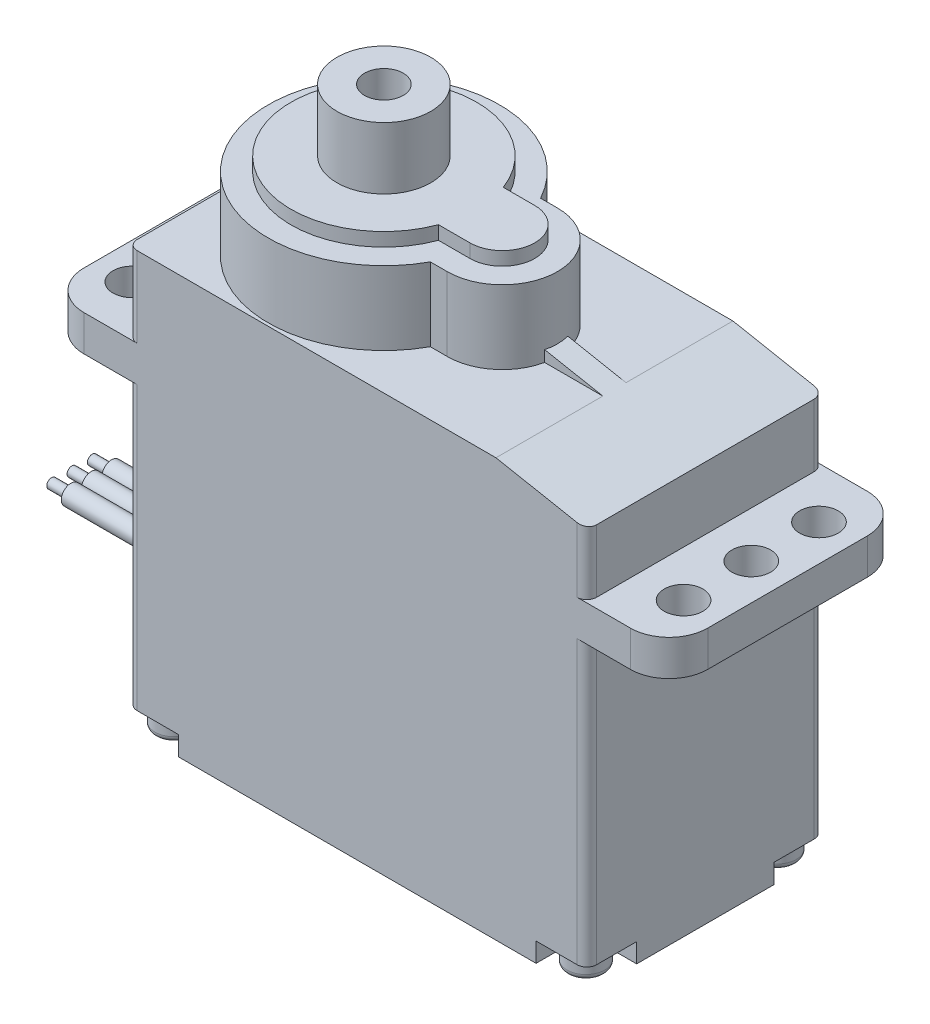
SolidWorks part; units mm, degrees
ref_plane "Front Plane" through (0, 0, 0) normal (0, 0, 1) x (1, 0, 0)
ref_plane "Top Plane" through (0, 0, 0) normal (0, 1, 0) x (1, 0, 0)
ref_plane "Right Plane" through (0, 0, 0) normal (1, 0, 0) x (0, 0, -1)
ref_axis "X-Axis" through (-88.99, 0, 0) along (1, 0, 0)
ref_axis "Y-Axis" through (0, 0, -88.99) along (0, 0, 1)
ref_axis "Z-Axis" through (0, 55, 0) along (0, -1, 0)
sketch "Sketch1" plane through (0, 0, 0) normal (0, 0, 1) x (1, 0, 0)
  line L0 (0, 0) -> (0, 13.7) construction
  line L1 (-7.13, 6) -> (11.92, 6)
  line L2 (-7.13, 6) -> (-7.13, 1.85)
  line L3 (-7.13, -15.6) -> (16.62, -15.6)
  line L4 (16.62, 5.1) -> (16.62, 1.85)
  line L5 (16.62, 1.85) -> (20.87, 1.85)
  line L6 (-11.38, 1.85) -> (-7.13, 1.85)
  line L7 (-11.38, 1.85) -> (-11.38, 0)
  line L8 (-11.38, 0) -> (-7.13, 0)
  line L9 (20.87, 1.85) -> (20.87, 0)
  line L10 (16.62, 0) -> (20.87, 0)
  line L11 (-7.13, 0) -> (-7.13, -15.6)
  line L12 (16.62, 0) -> (16.62, -15.6)
  line L13 (16.62, 5.1) -> (11.92, 6)
  line L14 (16.62, 0) -> (-7.13, 0) construction
  point P3 (4.745, 0)
  dimension "D1" = 1.85
  dimension "D2" = 32.25
  dimension "D3" = 23.75
  dimension "D4" = 15.6
  dimension "D5" = 21.6
  dimension "D6" = 7.13
  dimension "D7" = 16.62
  dimension "D8" = 0.9
  dimension "D9" = 4.7
  dimension "D10" = 29.3
  dimension "D11" = 4.745
extrude "Boss-Extrude1" add sketch "Sketch1" along normal mid plane 12.25
sketch "Sketch2" plane through (0, 6, 0) normal (0, 1, 0) x (1, 0, 0)
  line L0 (0, 0) -> (6.125, 0) construction
  line L1 (5.2515, -2.85) -> (6.125, -2.85)
  line L2 (6.125, 2.85) -> (5.2515, 2.85)
  line L3 (0, 0) -> (-5.975, 0) construction
  line L4 (6.125, 0) -> (8.975, 0) construction
  arc A0 (5.2515, 2.85) -> (5.2515, -2.85) centre (0, 0) ccw
  arc A1 (6.125, -2.85) -> (6.125, 2.85) centre (6.125, 0) ccw
  dimension "D1" = 11.95
  dimension "D2" = 5.7
  dimension "D3" = 14.95
extrude "Boss-Extrude2" add sketch "Sketch2" along normal blind 3.8
sketch "Sketch3" plane through (0, 9.8, 0) normal (0, 1, 0) x (1, 0, 0)
  line L0 (4.4983, -1.675) -> (6.125, -1.675)
  line L1 (6.125, 1.675) -> (4.4983, 1.675)
  line L2 (7.8, 0) -> (8.975, 0) construction
  line L3 (-4.8, 0) -> (-5.975, 0) construction
  arc A0 (4.4983, 1.675) -> (4.4983, -1.675) centre (0, 0) ccw
  arc A1 (6.125, -1.675) -> (6.125, 1.675) centre (6.125, 0) ccw
  arc A2 (6.125, -2.85) -> (6.125, 2.85) centre (6.125, 0) ccw construction
  arc A3 (5.2515, 2.85) -> (5.2515, -2.85) centre (0, 0) ccw construction
  dimension "D1" = 9.6
extrude "Boss-Extrude3" add sketch "Sketch3" along normal blind 0.7
sketch "Sketch4" plane through (0, 0, 0) normal (0, 1, 0) x (1, 0, 0)
  line L0 (-9.505, 0) -> (-7.13, 0) construction
  line L1 (-9.505, 3.5) -> (18.995, 3.5) construction
  line L2 (-9.505, 3.5) -> (-9.505, -3.5) construction
  line L3 (-9.505, -3.5) -> (18.995, -3.5) construction
  line L4 (18.995, 3.5) -> (18.995, -3.5) construction
  line L5 (18.995, 0) -> (16.62, 0) construction
  line L6 (-7.13, -6.125) -> (-7.13, 6.125) construction
  line L7 (16.62, -6.125) -> (16.62, 6.125) construction
  circle A0 centre (-9.505, 3.5) radius 1
  circle A1 centre (-9.505, -3.5) radius 1
  circle A2 centre (18.995, 3.5) radius 1
  circle A3 centre (18.995, -3.5) radius 1
  circle A4 centre (18.995, 0) radius 1
  circle A5 centre (-9.505, 0) radius 1
  dimension "D1" = 2
  dimension "D2" = 28.5
  dimension "D3" = 7
extrude "Cut-Extrude1" cut sketch "Sketch4" along normal through all
sketch "Sketch5" plane through (0, -15.6, 0) normal (0, -1, 0) x (1, 0, 0)
  line L0 (16.62, 6.125) -> (-7.13, -6.125) construction
  line L1 (16.62, 6.125) -> (13.995, 6.125)
  line L2 (16.62, 6.125) -> (16.62, 3.55)
  line L3 (16.62, 3.55) -> (15.295, 3.55)
  line L4 (13.995, 6.125) -> (13.995, 4.85)
  line L5 (16.62, -6.125) -> (13.995, -6.125)
  line L6 (16.62, -6.125) -> (16.62, -3.55)
  line L7 (16.62, -3.55) -> (15.295, -3.55)
  line L8 (13.995, -6.125) -> (13.995, -4.85)
  line L9 (-7.13, 6.125) -> (-4.505, 6.125)
  line L10 (-7.13, 6.125) -> (-7.13, 3.55)
  line L11 (-7.13, 3.55) -> (-5.805, 3.55)
  line L12 (-4.505, 6.125) -> (-4.505, 4.85)
  line L13 (-7.13, -6.125) -> (-4.505, -6.125)
  line L14 (-7.13, -6.125) -> (-7.13, -3.55)
  line L15 (-7.13, -3.55) -> (-5.805, -3.55)
  line L16 (-4.505, -6.125) -> (-4.505, -4.85)
  line L17 (-5.905, 4.95) -> (15.395, 4.95) construction
  line L18 (-5.905, 4.95) -> (-5.905, -4.95) construction
  line L19 (-5.905, -4.95) -> (15.395, -4.95) construction
  line L20 (15.395, 4.95) -> (15.395, -4.95) construction
  line L21 (-5.905, 4.95) -> (15.395, -4.95) construction
  arc A0 (13.995, -4.85) -> (15.295, -3.55) centre (15.295, -4.85) cw
  arc A1 (15.295, 3.55) -> (13.995, 4.85) centre (15.295, 4.85) cw
  arc A2 (-4.505, 4.85) -> (-5.805, 3.55) centre (-5.805, 4.85) cw
  arc A3 (-5.805, -3.55) -> (-4.505, -4.85) centre (-5.805, -4.85) cw
  circle A4 centre (-5.905, 4.95) radius 0.975
  circle A5 centre (-5.905, -4.95) radius 0.975
  circle A6 centre (15.395, -4.95) radius 0.975
  circle A7 centre (15.395, 4.95) radius 0.975
  point P36 (4.745, 0)
  dimension "D1" = 1.3
  dimension "D4" = 1.95
  dimension "D2" = 7.1
  dimension "D3" = 18.5
  dimension "D5" = 21.3
  dimension "D6" = 9.9
extrude "Cut-Extrude2" cut sketch "Sketch5" against normal blind 1
sketch "Sketch6" plane through (-7.13, 0, 0) normal (-1, 0, 0) x (0, 0, 1)
  line L0 (-1.05, -11.7) -> (1.05, -11.7) construction
  line L2 (6.125, 0) -> (-6.125, 0) construction
  circle A0 centre (0, -11.7) radius 0.5
  circle A1 centre (1.05, -11.7) radius 0.5
  circle A2 centre (-1.05, -11.7) radius 0.5
  dimension "D3" = 1
  dimension "D1" = 11.7
  dimension "D2" = 2.1
extrude "Boss-Extrude4" add sketch "Sketch6" along normal blind 8
sketch "Sketch7" plane through (-15.13, 0, 0) normal (-1, 0, 0) x (0, 0, 1)
  circle A0 centre (0, -11.7) radius 0.25
  circle A1 centre (1.05, -11.7) radius 0.25
  circle A2 centre (-1.05, -11.7) radius 0.25
  dimension "D1" = 0.5
extrude "Boss-Extrude5" add sketch "Sketch7" along normal blind 1
sketch "Sketch8" plane through (0, 0, 0) normal (0, 0, 1) x (1, 0, 0)
  line L0 (11.92, 6) -> (7.8, 6.7889)
  line L1 (7.8, 6.7889) -> (7.8, 6)
  line L2 (7.8, 6) -> (11.92, 6)
  line L3 (16.62, 5.1) -> (11.92, 6) construction
extrude "Boss-Extrude6" add sketch "Sketch8" along normal mid plane 1.2
sketch "Sketch9" plane through (0, 0, 0) normal (0, 0, 1) x (1, 0, 0)
  line L0 (1, 13.7) -> (2.425, 13.7)
  line L1 (2.425, 13.7) -> (2.425, 10.5)
  line L4 (2.425, 10.5) -> (1, 10.5)
  line L6 (1, 10.5) -> (1, 13.7)
  line L8 (4.4983, 10.5) -> (-4.8, 10.5) construction
  line L9 (0, 13.7) -> (0, 10.5) construction
  line L10 (0, 0) -> (0, 13.7) construction
  dimension "D1" = 2
  dimension "D4" = 4.85
revolve "Revolve1" add sketch "Sketch9" angle 360 about axis through (0, 55, 0) along (0, -1, 0)
fillet "Fillet1" radius 0.3 4 edges at (15.395, -15.6, -5.925) (15.395, -15.6, 3.975) (-5.905, -15.6, -5.925) (-5.905, -15.6, 3.975)
fillet "Fillet2" radius 2 4 edges at (20.87, 0.925, -6.125) (20.87, 0.925, 6.125) (-11.38, 0.925, 6.125) (-11.38, 0.925, -6.125)
fillet "Fillet3" radius 0.5 8 edges at (16.62, -7.3, -6.125) (16.62, 3.475, -6.125) (16.62, 3.475, 6.125) (16.62, -7.3, 6.125) (-7.13, -7.3, -6.125) (-7.13, 3.925, -6.125) (-7.13, 3.925, 6.125) (-7.13, -7.3, 6.125)
ref_axis "Axis1" through (-9.505, 1.85, 3.5) along (0, -1, 0)
ref_axis "Axis2" through (-9.505, 1.85, -3.5) along (0, -1, 0)
ref_axis "Axis3" through (18.995, 1.85, -3.5) along (0, -1, 0)
ref_axis "Axis4" through (18.995, 1.85, 3.5) along (0, -1, 0)
